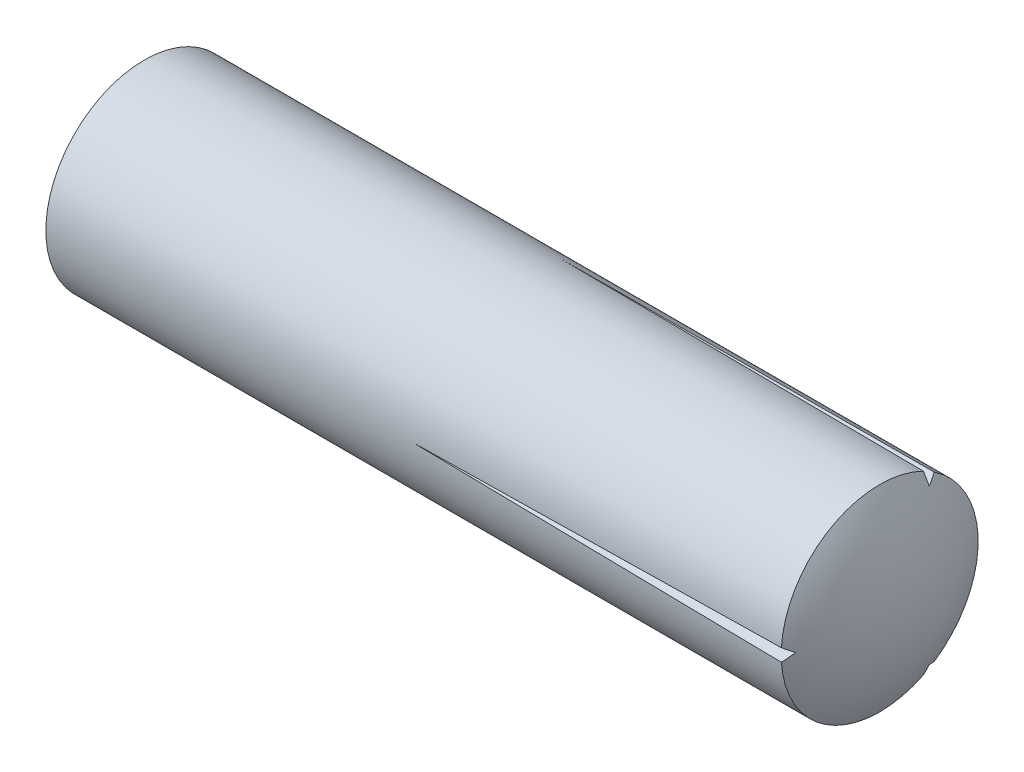
SolidWorks part; units mm, degrees
revolve "Base-Revolve" add sketch "Sketch1" angle 360 about L0
sketch "Sketch1" plane through (0, 0, 0) normal (0, 0, 1) x (1, 0, 0)
  line L0 (-40, 0) -> (40, 0) construction
  line L1 (-100, 0) -> (-100, 1.25)
  line L2 (-96.6819, 12.5) -> (-3.3494, 12.5)
  line L4 (0, 0) -> (-100, 0)
  arc A0 (-96.6819, 12.5) -> (-100, 1.25) centre (-75.0313, 0) ccw
  arc A1 (0, 0) -> (-3.3494, 12.5) centre (-25, 0) ccw
  dimension "D2" = 25
  dimension "D3" = 2.5
ref_plane "Plane1" through (0, 0, 0) normal (0, 0, 1) x (1, 0, 0)
ref_plane "Plane2" through (0, 0, 0) normal (0, 1, 0) x (1, 0, 0)
ref_plane "Plane3" through (0, 0, 0) normal (1, 0, 0) x (0, 0, -1)
sketch "Sketch2" plane through (0, 0, 0) normal (1, 0, 0) x (0, 0, -1)
  line L0 (0, 0) -> (-15, 0) construction
  line L1 (-11.25, 0) -> (-12.5, 0.8753)
  line L2 (-11.25, 0) -> (-12.5, -0.8753)
  line L3 (-12.5, -0.8753) -> (-12.5, 0.8753)
  circle A0 centre (0, 0) radius 11.25 construction
  circle A1 centre (0, 0) radius 12.5 construction
  dimension "D1" = 22.5
  dimension "D2" = 70
  dimension "D3" = 35
sketch "Sketch4" plane through (0, 0, 0) normal (0, 1, 0) x (1, 0, 0)
  line L0 (-110, 0) -> (10, 0) construction
  line L1 (-40, 0) -> (40, 0) construction
  line L2 (0, -11.25) -> (-50, -12.5)
  dimension "D1" = 22.5
  dimension "D2" = 50
  dimension "D3" = 25
sweep "Cut-Sweep1" cut profiles "Sketch2" path "Sketch4"
pattern_circular "CirPattern1" count 3 over 360 about axis through (-40, 0, 0) along (1, 0, 0) of "Cut-Sweep1"
equation "\"D1@Sketch1\" = \"Diameter@Sketch1\""
equation "\"D2@Sketch1\" = \"Diameter@Sketch1\""
equation "\"D3@Sketch1\" = \"Diameter@Sketch1\" * .1"
equation "\"D1@Sketch2\" = \"Diameter@Sketch1\" * .9"
equation "\"D3@Sketch2\" = \"D2@Sketch2\" / 2"
equation "\"D1@Sketch4\" = \"D1@Sketch2\""
equation "\"D2@Sketch4\" = \"Length@Sketch1\" / 2"
equation "\"D3@Sketch4\" = \"Diameter@Sketch1\""
